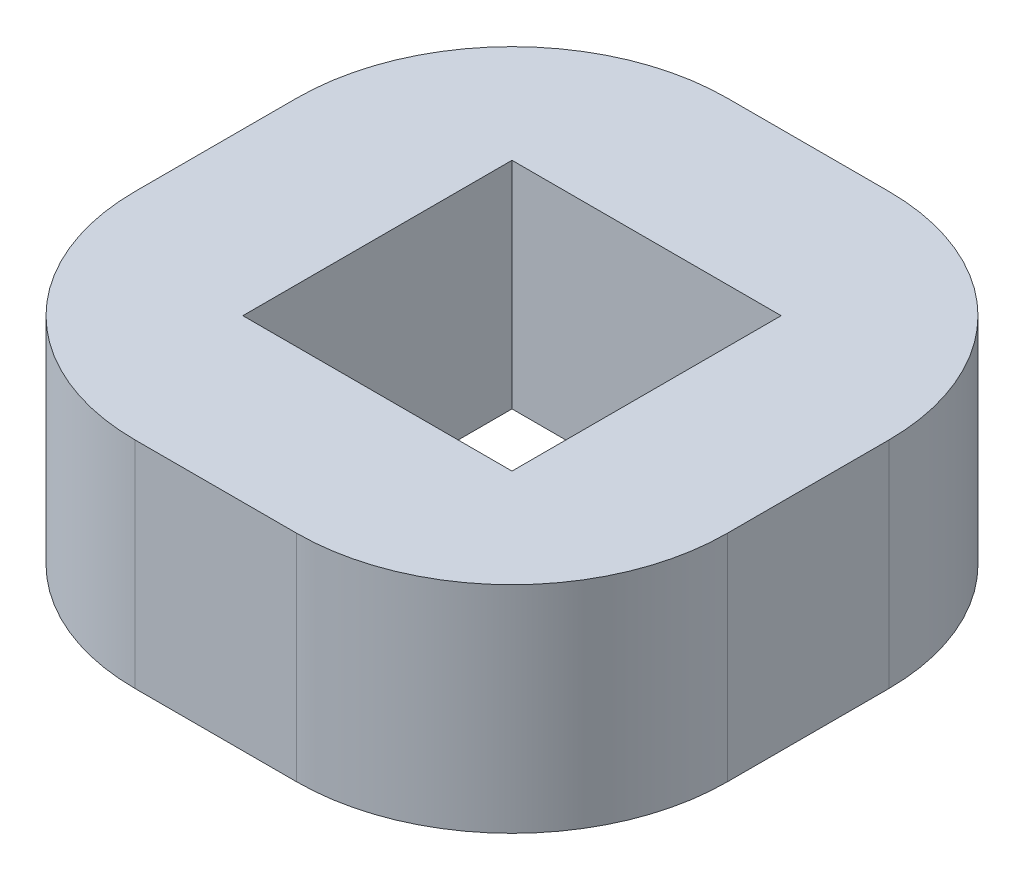
SolidWorks part; units mm, degrees
ref_plane "Front Plane" through (0, 0, 0) normal (0, 0, 1) x (1, 0, 0)
ref_plane "Top Plane" through (0, 0, 0) normal (0, 1, 0) x (1, 0, 0)
ref_plane "Right Plane" through (0, 0, 0) normal (1, 0, 0) x (0, 0, -1)
sketch "Sketch1" plane through (0, 0, 0) normal (0, 1, 0) x (1, 0, 0)
  line L1 (-12.5, -12.5) -> (12.5, -12.5)
  line L2 (-12.5, -12.5) -> (-12.5, 12.5)
  line L3 (-12.5, 12.5) -> (12.5, 12.5)
  line L4 (12.5, -12.5) -> (12.5, 12.5)
  line L5 (-12.5, -12.5) -> (12.5, 12.5) construction
  line L6 (-12.5, 12.5) -> (12.5, -12.5) construction
  line L7 (27.5, -27.5) -> (-27.5, -27.5)
  line L8 (27.5, -27.5) -> (27.5, 27.5)
  line L9 (27.5, 27.5) -> (-27.5, 27.5)
  line L10 (-27.5, -27.5) -> (-27.5, 27.5)
  line L11 (27.5, -27.5) -> (-27.5, 27.5) construction
  line L12 (27.5, 27.5) -> (-27.5, -27.5) construction
  circle A1 centre (0, 0) radius 27.5
  dimension "D1" = 25
  dimension "D2" = 55
  dimension "D3" = 25
  dimension "D4" = 55
  dimension "D5" = 55
extrude "Boss-Extrude1" add sketch "Sketch1" along normal blind 20 contours A1 L4 L1 L2 L3 | A1 L9 L10 | A1 L8 L9 | A1 L7 L8 | A1 L10 L7 region at (21.3574, 0, 21.3574) region at (-21.3574, 0, 21.3574) region at (-18.8954, 0, 18.8954) region at (21.3574, 0, -21.3574) region at (-21.3574, 0, -21.3574)
fillet "Fillet1" radius 20 4 edges at (-27.5, 10, -27.5) (27.5, 10, -27.5) (27.5, 10, 27.5) (-27.5, 10, 27.5)
